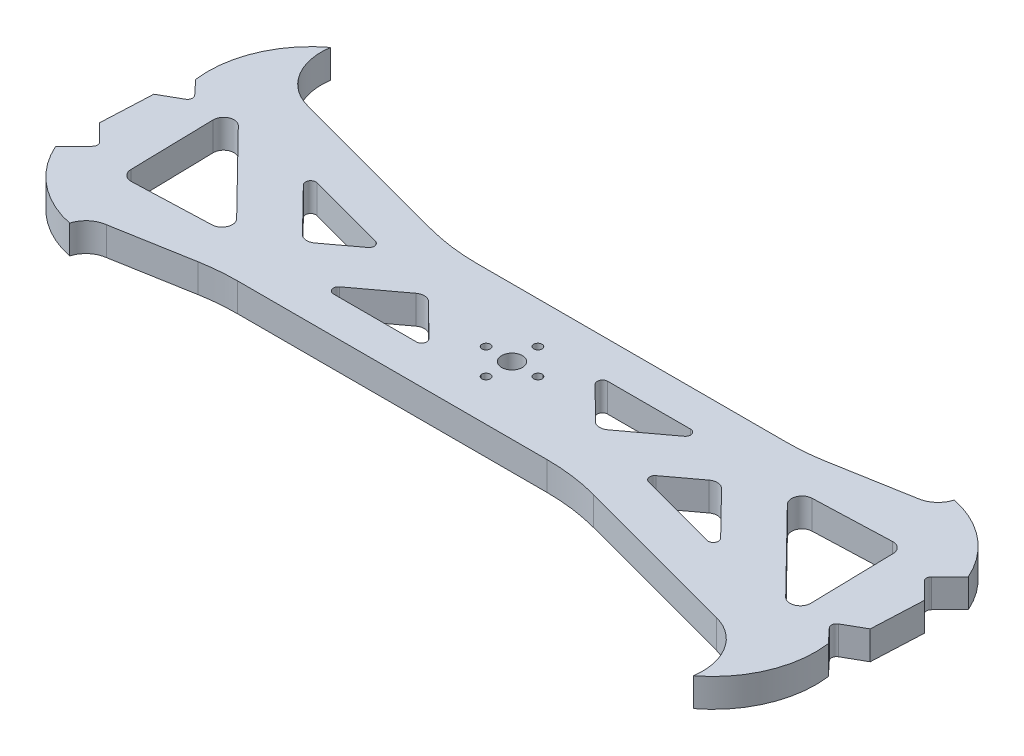
SolidWorks part; units mm, degrees
material "AR400 Steel"
ref_plane "Front Plane" through (0, 0, 0) normal (0, 0, 1) x (1, 0, 0)
ref_plane "Top Plane" through (0, 0, 0) normal (0, 1, 0) x (1, 0, 0)
ref_plane "Right Plane" through (0, 0, 0) normal (1, 0, 0) x (0, 0, -1)
sketch "Sketch1" plane through (0, 0, 0) normal (0, 1, 0) x (1, 0, 0)
  line L1 (-101.6, 44.45) -> (101.6, 44.45)
  line L2 (-101.6, 44.45) -> (-101.6, -44.45)
  line L3 (-101.6, -44.45) -> (101.6, -44.45)
  line L4 (101.6, 44.45) -> (101.6, -44.45)
  line L5 (-101.6, 44.45) -> (101.6, -44.45) construction
  line L6 (-101.6, -44.45) -> (101.6, 44.45) construction
  point P0 (0, 0)
  dimension "D1" = 203.2
  dimension "D2" = 88.9
extrude "Boss-Extrude1" add sketch "Sketch1" along normal mid plane 6.985
sketch "Sketch2" plane through (0, 3.4925, 0) normal (0, 1, 0) x (1, 0, 0)
  line L0 (3.7777, 0) -> (0, 0) construction
  line L1 (-129.3538, 0) -> (129.3538, 0) construction
  line L2 (0, 76.2705) -> (0, -76.2705) construction
  line L3 (31.75, 16.51) -> (-31.75, 16.51)
  line L4 (31.75, -16.51) -> (-31.75, -16.51)
  line L5 (31.75, -16.51) -> (81.28, -29.7815)
  line L6 (101.6, -44.45) -> (101.6, 44.45) construction
  line L7 (78.74, 20.6528) -> (55.245, 16.51)
  line L8 (-101.6, -44.45) -> (101.6, -44.45) construction
  line L9 (87.3981, 8.5297) -> (88.057, -21.079)
  line L10 (31.75, 16.51) -> (55.245, 16.51)
  line L11 (101.6, 10.2162) -> (96.2187, 4.8349)
  line L12 (96.2187, 4.8349) -> (101.2145, -0.1609)
  line L13 (100.6329, -12.8476) -> (94.3005, -16.4671)
  line L15 (101.2145, -0.1609) -> (100.6329, -12.8476)
  line L16 (94.3005, -16.4671) -> (98.6386, -21.1044)
  line L17 (87.3981, 8.5297) -> (60.0219, 7.543)
  line L19 (40.0521, 7.543) -> (12.8225, 7.543)
  line L21 (88.057, -21.079) -> (60.0219, 7.543)
  line L22 (66.3202, -15.2546) -> (39.7424, -8.1331)
  line L23 (51.0775, 0.3071) -> (66.3202, -15.2546)
  line L24 (51.0775, 0.3071) -> (39.7424, -8.1331)
  line L25 (24.4883, -4.0458) -> (40.0521, 7.543)
  line L26 (12.8225, 7.543) -> (24.4883, -4.0458)
  line L43 (-31.75, 16.51) -> (-81.28, 29.7815)
  line L44 (-78.74, -20.6528) -> (-55.245, -16.51)
  line L45 (-87.3981, -8.5297) -> (-88.057, 21.079)
  line L46 (-31.75, -16.51) -> (-55.245, -16.51)
  line L47 (-101.6, -10.2162) -> (-96.2187, -4.8349)
  line L48 (-96.2187, -4.8349) -> (-101.2145, 0.1609)
  line L49 (-100.6329, 12.8476) -> (-94.3005, 16.4671)
  line L50 (-101.2145, 0.1609) -> (-100.6329, 12.8476)
  line L51 (-94.3005, 16.4671) -> (-98.6386, 21.1044)
  line L52 (-87.3981, -8.5297) -> (-60.0219, -7.543)
  line L53 (-40.0521, -7.543) -> (-12.8225, -7.543)
  line L54 (-88.057, 21.079) -> (-60.0219, -7.543)
  line L55 (-66.3202, 15.2546) -> (-39.7424, 8.1331)
  line L56 (-51.0775, -0.3071) -> (-66.3202, 15.2546)
  line L57 (-51.0775, -0.3071) -> (-39.7424, 8.1331)
  line L58 (-24.4883, 4.0458) -> (-40.0521, -7.543)
  line L59 (-12.8225, -7.543) -> (-24.4883, 4.0458)
  arc A0 (81.28, -29.7815) -> (88.9, -44.45) centre (75.0952, -42.3079) cw
  arc A1 (78.74, 20.6528) -> (83.5933, 24.8237) centre (77.9809, 26.4453) ccw
  arc A2 (83.5933, 24.8237) -> (101.6, 10.2162) centre (78.3588, -0.0311) cw
  arc A3 (98.6386, -21.1044) -> (88.9, -44.45) centre (73.6757, -24.3952) cw
  circle A4 centre (0, 0) radius 2.54
  arc A9 (-81.28, 29.7815) -> (-88.9, 44.45) centre (-75.0952, 42.3079) cw
  arc A10 (-78.74, -20.6528) -> (-83.5933, -24.8237) centre (-77.9809, -26.4453) ccw
  arc A11 (-83.5933, -24.8237) -> (-101.6, -10.2162) centre (-78.3588, 0.0311) cw
  arc A12 (-98.6386, 21.1044) -> (-88.9, 44.45) centre (-73.6757, 24.3952) cw
  point P6 (0, 0)
  point P8 (0, 0)
  point P12 (0, 16.51)
  line M6 (101.6, -44.45) -> (101.6, 44.45)
  line M7 (101.6, 44.45) -> (-101.6, 44.45)
  line M8 (-101.6, 44.45) -> (-101.6, -44.45)
  line M9 (-101.6, -44.45) -> (101.6, -44.45)
  dimension "D4" = 22.86
  dimension "D7" = 12.7
  dimension "D6" = 46.99
  dimension "D1" = 33.02
  dimension "D2" = 195
  dimension "D3" = 20.32
  dimension "D5" = 190
extrude "Cut-Extrude1" cut sketch "Sketch2" against normal through all contours L16 A3 L11 L12 L15 L13 M9 M6 | A9 L43 L3 L10 L7 A1 A2 M6 M7 | L23 L24 L22 | L19 L26 L25 | L53 L59 L58 | L56 L57 L55 | L54 L45 L52 | L51 A12 L47 L48 L50 L49 M7 M8 | A10 A11 A0 L5 L4 L46 L44 M8 M9 | L21 L17 L9 region at (11.615, 3.4925, -31.6109) region at (-97.4317, 3.4925, -34.305) region at (101.0388, 3.4925, 17.1169) region at (-11.615, 3.4925, 31.6109) region at (25.7877, 3.4925, -3.6801) region at (52.38, 3.4925, 7.6936) region at (-78.4923, 3.4925, -1.6688) region at (-25.7877, 3.4925, 3.6801) region at (-52.38, 3.4925, -7.6936)
sketch "Sketch3" plane through (0, 3.4925, 0) normal (0, 1, 0) x (1, 0, 0)
  circle A0 centre (0, 0) radius 2.54
extrude "Cut-Extrude2" cut sketch "Sketch3" against normal through all contours A0
sketch "Sketch4" plane through (0, 3.4925, 0) normal (0, 1, 0) x (1, 0, 0)
  line L0 (0, 0) -> (0, -21.5527) construction
  circle A0 centre (0, -6.35) radius 1.016
  dimension "D1" = 6.35
extrude "Cut-Extrude3" cut sketch "Sketch4" against normal through all
pattern_circular "CirPattern1" count 4 over 360 about axis through (0, 3.4925, 0) along (0, 1, 0) of "Cut-Extrude3"
fillet "Fillet1" radius 2.54 7 edges at (-60.0219, 0, 7.543) (-87.3981, 0, 8.5297) (-88.057, 0, -21.079) (51.0775, 0, -0.3071) (88.057, 0, 21.079) (60.0219, 0, -7.543) (87.3981, 0, -8.5297)
fillet "Fillet2" radius 1.27 8 edges at (-66.3202, 0, -15.2546) (-39.7424, 0, -8.1331) (-40.0521, 0, 7.543) (-12.8225, 0, 7.543) (12.8225, 0, -7.543) (40.0521, 0, -7.543) (39.7424, 0, 8.1331) (66.3202, 0, 15.2546)
fillet "Fillet3" radius 2.54 3 edges at (24.4883, 0, 4.0458) (-24.4883, 0, -4.0458) (-51.0775, 0, 0.3071)
fillet "Fillet5" radius 1.27 4 edges at (94.3005, 0, 16.4671) (96.2187, 0, -4.8349) (-94.3005, 0, -16.4671) (-96.2187, 0, 4.8349)
fillet "Fillet6" radius 50.8 2 edges at (-31.75, 0, -16.51) (31.75, 0, 16.51)
fillet "Fillet7" radius 12.7 2 edges at (81.28, 0, 29.7815) (-81.28, 0, -29.7815)
fillet "Fillet8" radius 50.8 2 edges at (55.245, 0, -16.51) (-55.245, 0, 16.51)
